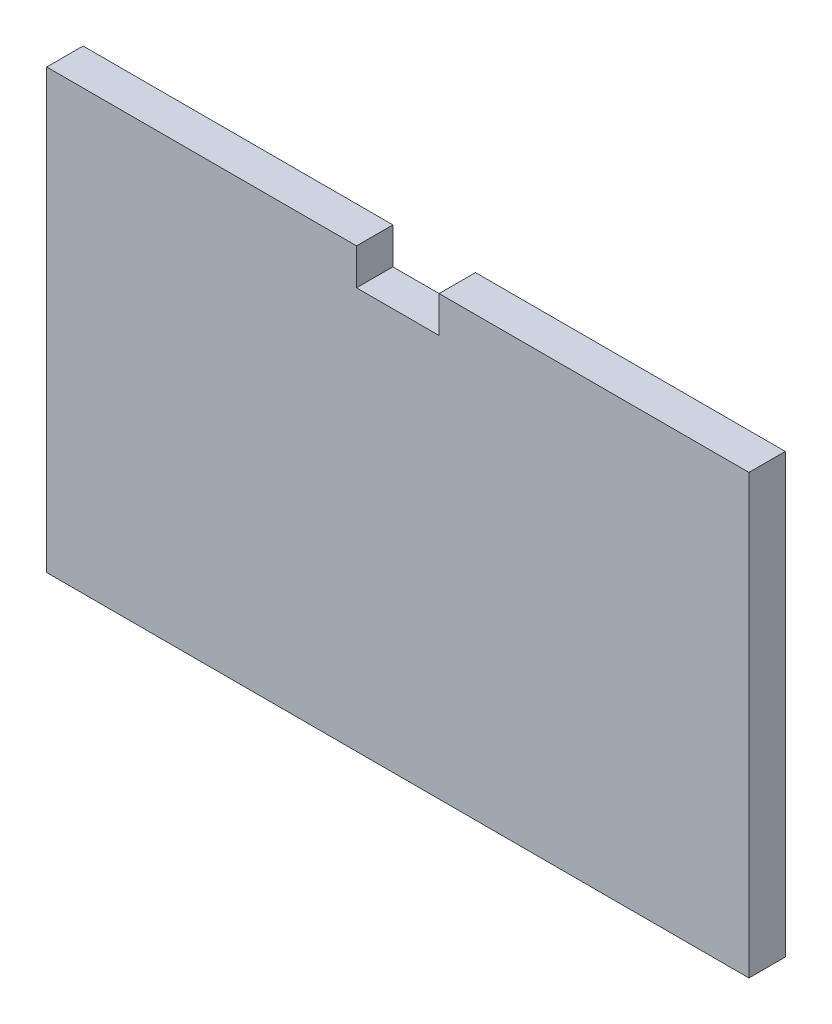
SolidWorks part; units mm, degrees
ref_plane "Front Plane" through (0, 0, 0) normal (0, 0, 1) x (1, 0, 0)
ref_plane "Top Plane" through (0, 0, 0) normal (0, 1, 0) x (1, 0, 0)
ref_plane "Right Plane" through (0, 0, 0) normal (1, 0, 0) x (0, 0, -1)
sketch "Sketch1" plane through (0, 0, 0) normal (0, 0, 1) x (1, 0, 0)
  line L0 (-6.35, 33.655) -> (-6.35, 28.067)
  line L1 (-53.975, -33.655) -> (53.975, -33.655)
  line L2 (-53.975, -33.655) -> (-53.975, 33.655)
  line L3 (-53.975, 33.655) -> (-6.35, 33.655)
  line L4 (53.975, -33.655) -> (53.975, 33.655)
  line L5 (-53.975, -33.655) -> (53.975, 33.655) construction
  line L6 (-53.975, 33.655) -> (53.975, -33.655) construction
  line L7 (-6.35, 28.067) -> (6.35, 28.067)
  line L8 (6.35, 28.067) -> (6.35, 33.655)
  line L9 (6.35, 33.655) -> (53.975, 33.655)
  point P0 (0, 0)
  dimension "D1" = 107.95
  dimension "D2" = 67.31
  dimension "D3" = 5.588
  dimension "D4" = 12.7
extrude "Boss-Extrude1" add sketch "Sketch1" along normal mid plane 5.588
